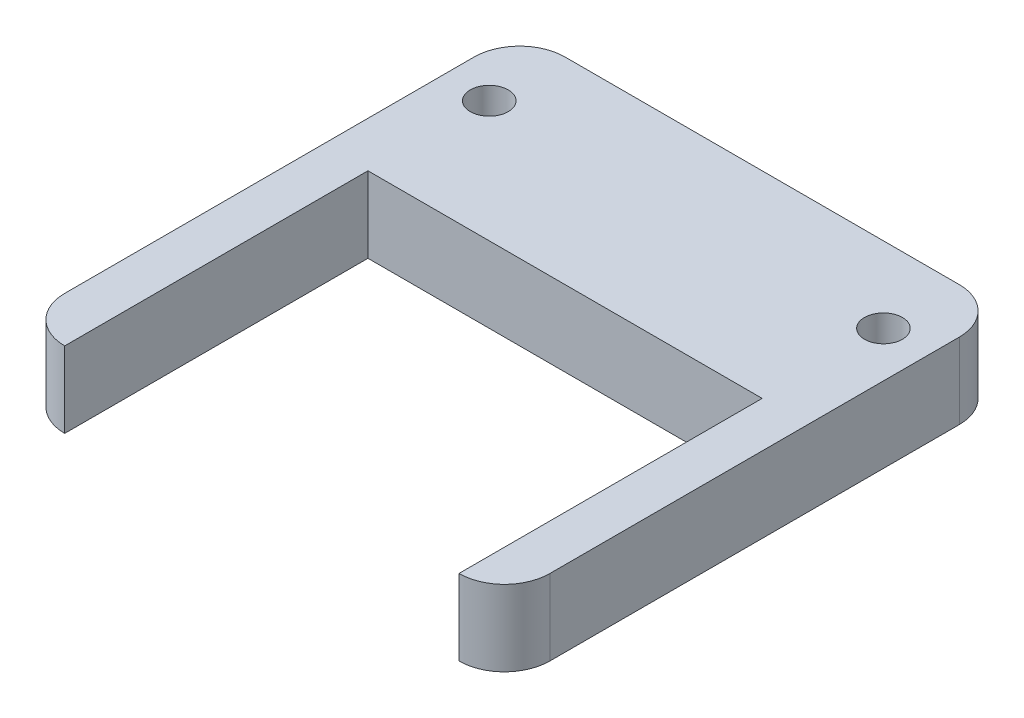
SolidWorks part; units mm, degrees
ref_plane "Front Plane" through (0, 0, 0) normal (0, 0, 1) x (1, 0, 0)
ref_plane "Top Plane" through (0, 0, 0) normal (0, 1, 0) x (1, 0, 0)
ref_plane "Right Plane" through (0, 0, 0) normal (1, 0, 0) x (0, 0, -1)
sketch "Sketch1" plane through (0, 0, 0) normal (0, 1, 0) x (1, 0, 0)
  line L0 (29, 0) -> (32, 0)
  line L1 (3, 0) -> (0, 0)
  line L2 (0, 0) -> (0, 33)
  line L3 (0, 33) -> (32, 33)
  line L4 (32, 0) -> (32, 33)
  line L6 (3, 0) -> (3, 20)
  line L7 (3, 20) -> (29, 20)
  line L8 (29, 0) -> (29, 20)
  circle A0 centre (3, 28) radius 1.25
  circle A1 centre (29, 28) radius 1.25
  point P13 (16, 20)
  point P14 (0, 0)
  point P15 (16, 33)
  dimension "D3" = 2.5
  dimension "D1" = 5
  dimension "D2" = 32
  dimension "D4" = 3
  dimension "D5" = 3
  dimension "D6" = 8
  dimension "D7" = 26
  dimension "D8" = 20
extrude "Boss-Extrude1" add sketch "Sketch1" along normal blind 5
fillet "Fillet1" radius 3 4 edges at (0, 2.5, -33) (32, 2.5, -33) (32, 2.5, 0) (0, 2.5, 0)
